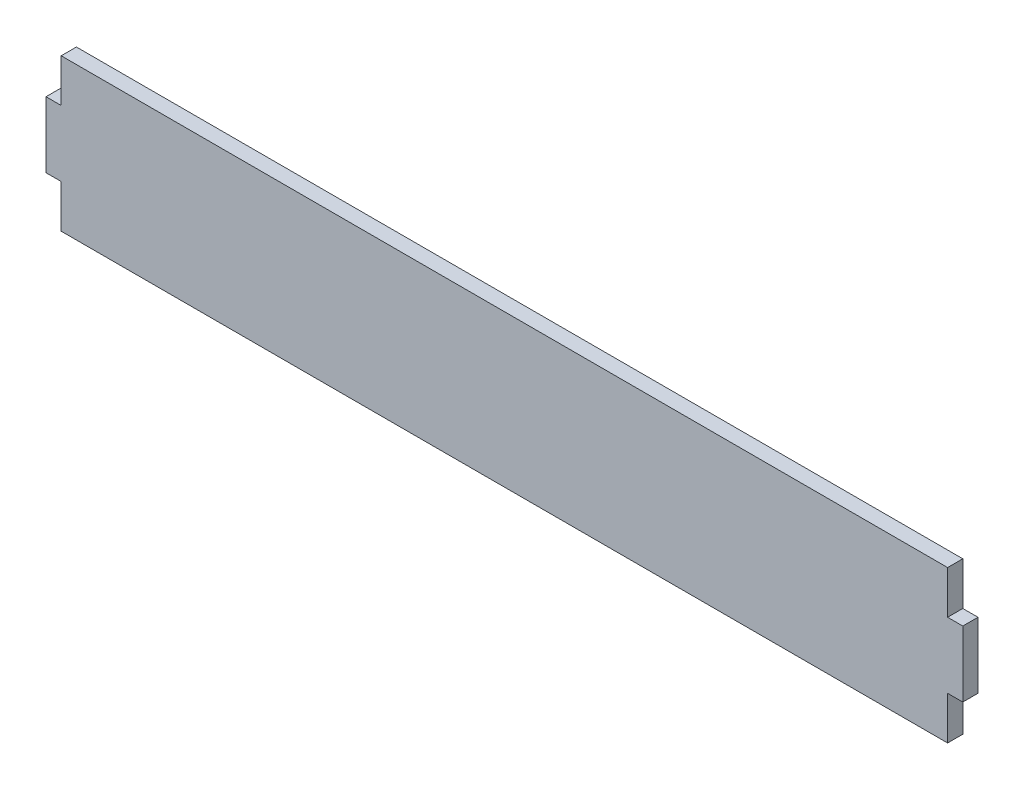
SolidWorks part; units mm, degrees
ref_plane "Front Plane" through (0, 0, 0) normal (0, 0, 1) x (1, 0, 0)
ref_plane "Top Plane" through (0, 0, 0) normal (0, 1, 0) x (1, 0, 0)
ref_plane "Right Plane" through (0, 0, 0) normal (1, 0, 0) x (0, 0, -1)
sketch "Sketch1" plane through (0, 0, 0) normal (0, 0, 1) x (1, 0, 0)
  line L0 (3, 21.5) -> (3, 30)
  line L1 (3, 0) -> (178, 0)
  line L3 (3, 30) -> (178, 30)
  line L5 (0, 21.5) -> (3, 21.5)
  line L6 (0, 21.5) -> (0, 8.5)
  line L7 (0, 8.5) -> (3, 8.5)
  line L10 (0, 0) -> (3, 0) construction
  line L11 (3, 8.5) -> (3, 0)
  line L12 (0, 8.5) -> (0, 0) construction
  line L13 (90.5, 15) -> (90.5, 3.5137) construction
  line L14 (0, 15) -> (181, 15) construction
  line L15 (181, -72.2342) -> (181, 60.9201) construction
  line L16 (178, 8.5) -> (178, 0)
  line L17 (181, 8.5) -> (178, 8.5)
  line L18 (178, 21.5) -> (178, 30)
  line L19 (181, 21.5) -> (178, 21.5)
  line L20 (181, 21.5) -> (181, 8.5)
  dimension "D1" = 30
  dimension "D2" = 13
  dimension "D3" = 3
extrude "Boss-Extrude1" add sketch "Sketch1" along normal blind 3
